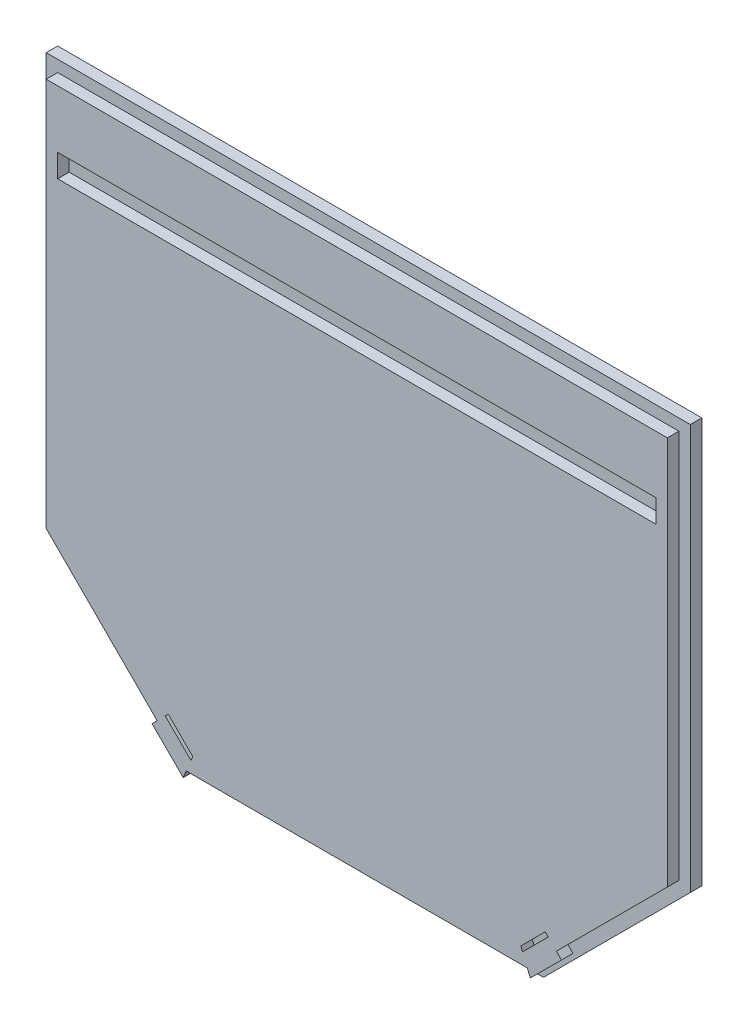
SolidWorks part; units mm, degrees
ref_plane "Front Plane" through (0, 0, 0) normal (0, 0, 1) x (1, 0, 0)
ref_plane "Top Plane" through (0, 0, 0) normal (0, 1, 0) x (1, 0, 0)
ref_plane "Right Plane" through (0, 0, 0) normal (1, 0, 0) x (0, 0, -1)
sketch "Sketch1" plane through (0, 0, 0) normal (0, 0, 1) x (1, 0, 0)
  line L0 (0, 0) -> (355.6, 0)
  line L1 (0, 0) -> (0, -223.774)
  line L2 (81.026, -304.8) -> (274.574, -304.8)
  line L3 (355.6, -223.774) -> (355.6, 0)
  line L4 (81.026, -304.8) -> (63.0655, -286.8395)
  line L5 (63.0655, -286.8395) -> (0, -223.774)
  line L6 (177.8, -304.8) -> (177.8, 0) construction
  line L7 (292.5345, -286.8395) -> (355.6, -223.774)
  line L8 (274.574, -304.8) -> (292.5345, -286.8395)
  dimension "D1" = 355.6
  dimension "D2" = 193.548
  dimension "D4" = 25.4
  dimension "D5" = 45
  dimension "D9" = 304.8
extrude "Boss-Extrude1" add sketch "Sketch1" along normal blind 12.7
sketch "Sketch2" plane through (0, 0, 12.7) normal (0, 0, 1) x (1, 0, 0)
  line L0 (6.35, -221.1437) -> (67.6075, -282.4012)
  line L1 (83.6563, -298.45) -> (271.9437, -298.45)
  line L2 (287.9925, -282.4012) -> (349.25, -221.1437)
  line L3 (349.25, -221.1437) -> (349.25, -6.35)
  line L4 (349.25, -6.35) -> (6.35, -6.35)
  line L5 (6.35, -6.35) -> (6.35, -221.1437)
  line L6 (0, -223.774) -> (81.026, -304.8) construction
  line L7 (81.026, -304.8) -> (274.574, -304.8) construction
  line L8 (274.574, -304.8) -> (355.6, -223.774) construction
  line L9 (355.6, -223.774) -> (355.6, 0) construction
  line L10 (0, 0) -> (0, -223.774) construction
  line L11 (355.6, 0) -> (0, 0) construction
  line L21 (81.026, -304.8) -> (83.6563, -298.45) construction
  line L23 (73.3233, -276.6854) -> (73.0994, -276.9093) construction
  line L24 (64.7877, -285.221) -> (82.0045, -302.4378)
  line L25 (82.0045, -302.4378) -> (83.6563, -298.45)
  line L26 (64.7877, -285.221) -> (67.6075, -282.4012)
  line L27 (0, 0) -> (0, -223.774)
  line L28 (0, -223.774) -> (81.026, -304.8)
  line L29 (81.026, -304.8) -> (274.574, -304.8)
  line L30 (274.574, -304.8) -> (355.6, -223.774)
  line L31 (355.6, -223.774) -> (355.6, 0)
  line L32 (355.6, 0) -> (0, 0)
  line L33 (177.8, -298.45) -> (177.8, 0) construction
  line L34 (12.7, -38.1) -> (342.9, -38.1)
  line L35 (12.7, -38.1) -> (12.7, -50.8)
  line L36 (12.7, -50.8) -> (342.9, -50.8)
  line L37 (342.9, -38.1) -> (342.9, -50.8)
  line L38 (273.5955, -302.4378) -> (271.9437, -298.45)
  line L39 (290.8123, -285.221) -> (273.5955, -302.4378)
  line L40 (290.8123, -285.221) -> (287.9925, -282.4012)
  line L41 (271.9437, -298.45) -> (349.25, -221.1437) construction
  line L42 (6.35, -221.1437) -> (83.6563, -298.45) construction
  line M13 (0, 0) -> (0, -223.774)
  line M14 (0, -223.774) -> (81.026, -304.8)
  line M15 (81.026, -304.8) -> (274.574, -304.8)
  line M16 (274.574, -304.8) -> (355.6, -223.774)
  line M17 (355.6, -223.774) -> (355.6, 0)
  line M18 (355.6, 0) -> (0, 0)
  dimension "D2" = 6.35
  dimension "D3" = 6.35
  dimension "D4" = 6.35
  dimension "D5" = 6.35
  dimension "D6" = 6.35
  dimension "D7" = 6.35
  dimension "D8" = 6.35
  dimension "D9" = 50.8
  dimension "D10" = 12.7
  dimension "D11" = 2.3622
extrude "Cut-Extrude1" cut sketch "Sketch2" against normal blind 6.35 contours L37 L34 L35 L36 | L5 L4 L3 L2 L1 L0 M18 M13 M14 M15 M16 M17 region at (177.8, -4.6835, 12.7) region at (177.8, -44.45, 12.7)
sketch "Sketch3" plane through (0, 0, 12.7) normal (0, 0, 1) x (1, 0, 0)
  line L0 (177.8, -304.8) -> (177.8, 0) construction
  line L1 (81.026, -304.8) -> (274.574, -304.8) construction
  line L2 (355.6, 0) -> (0, 0) construction
  line L3 (81.026, -304.8) -> (83.6563, -298.45) construction
  line L4 (86.2865, -292.1) -> (72.0977, -277.9112)
  line L5 (86.2865, -292.1) -> (87.265, -289.7378)
  line L8 (72.0977, -277.9112) -> (73.768, -276.2409)
  line L9 (73.768, -276.2409) -> (87.265, -289.7378)
  line L10 (283.5023, -277.9112) -> (281.832, -276.2409)
  line L11 (269.3135, -292.1) -> (283.5023, -277.9112)
  line L12 (269.3135, -292.1) -> (268.335, -289.7378)
  line L13 (281.832, -276.2409) -> (268.335, -289.7378)
  line L14 (11.7799, -215.7138) -> (6.35, -221.1437) construction
  line L15 (6.35, -221.1437) -> (67.6075, -282.4012) construction
  dimension "D1" = 20.066
  dimension "D2" = 6.35
  dimension "D3" = 2.3622
  dimension "D4" = 90
  dimension "D5" = 67.5
extrude "Cut-Extrude3" cut sketch "Sketch3" against normal blind 6.35
